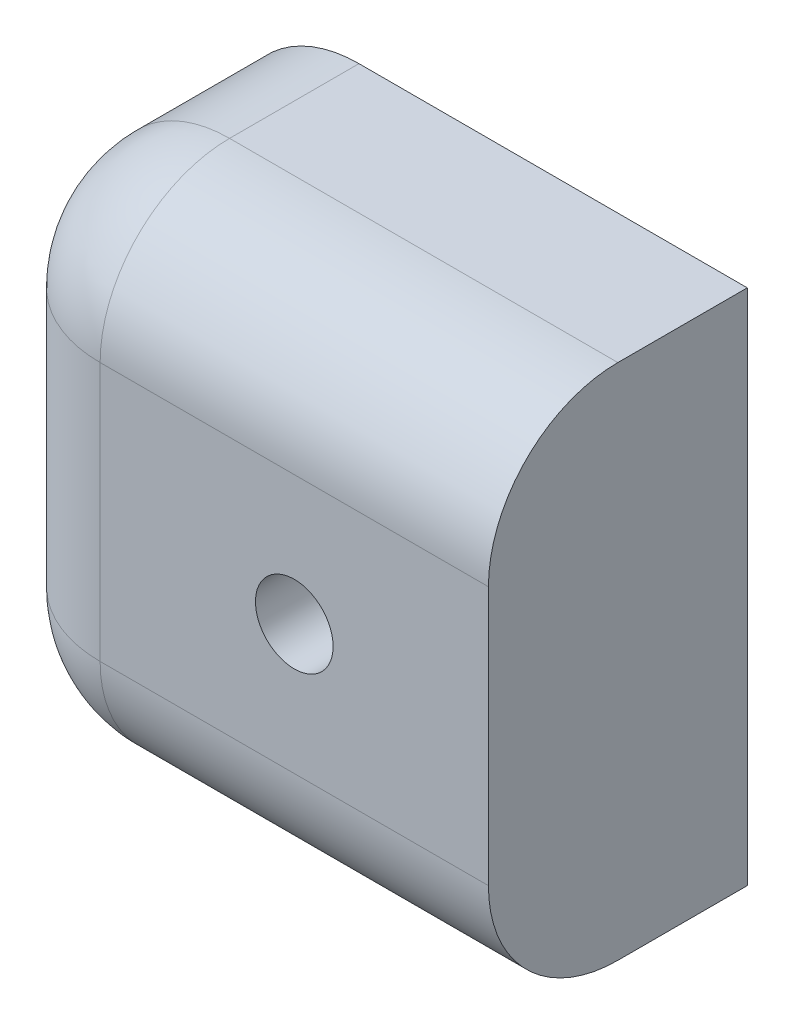
SolidWorks part; units mm, degrees
material "Plastique personnalisé"
ref_plane "Plan de face" through (0, 0, 0) normal (0, 0, 1) x (1, 0, 0)
ref_plane "Plan de dessus" through (0, 0, 0) normal (0, 1, 0) x (1, 0, 0)
ref_plane "Plan de droite" through (0, 0, 0) normal (1, 0, 0) x (0, 0, -1)
sketch "Esquisse1" plane through (0, 0, 0) normal (0, 0, 1) x (1, 0, 0)
  line L1 (5, 0) -> (20, 0)
  line L2 (0, 5) -> (0, 15)
  line L3 (5, 20) -> (20, 20)
  line L4 (20, 0) -> (20, 20)
  arc A0 (5, 0) -> (0, 5) centre (5, 5) cw
  arc A1 (0, 15) -> (5, 20) centre (5, 15) cw
  point P7 (0, 0)
  point P10 (0, 20)
  dimension "D3" = 5
  dimension "D1" = 20
  dimension "D2" = 20
extrude "Boss.-Extru.1" add sketch "Esquisse1" along normal blind 10
fillet "Congé1" radius 5 5 edges at (12.5, 20, 10) (1.4645, 18.5355, 10) (0, 10, 10) (12.5, 0, 10) (1.4645, 1.4645, 10)
sketch "Esquisse2" plane through (0, 0, 10) normal (0, 0, 1) x (1, 0, 0)
  line L0 (20, 15) -> (5, 5) construction
  line L1 (5, 5) -> (5, 15) construction
  line L2 (5, 15) -> (20, 5) construction
  circle A0 centre (12.5, 10) radius 1.5
extrude "Enlèv. mat.-Extru.1" cut sketch "Esquisse2" against normal blind 10
sketch "Esquisse3" plane through (0, 0, 10) normal (0, 0, 1) x (1, 0, 0)
  line L0 (5, 9.818) -> (26.951, 9.818) construction
  line L1 (5, 15) -> (5, 5) construction
ref_axis "Axe1" through (5, 9.818, 10) along (1, 0, 0)
